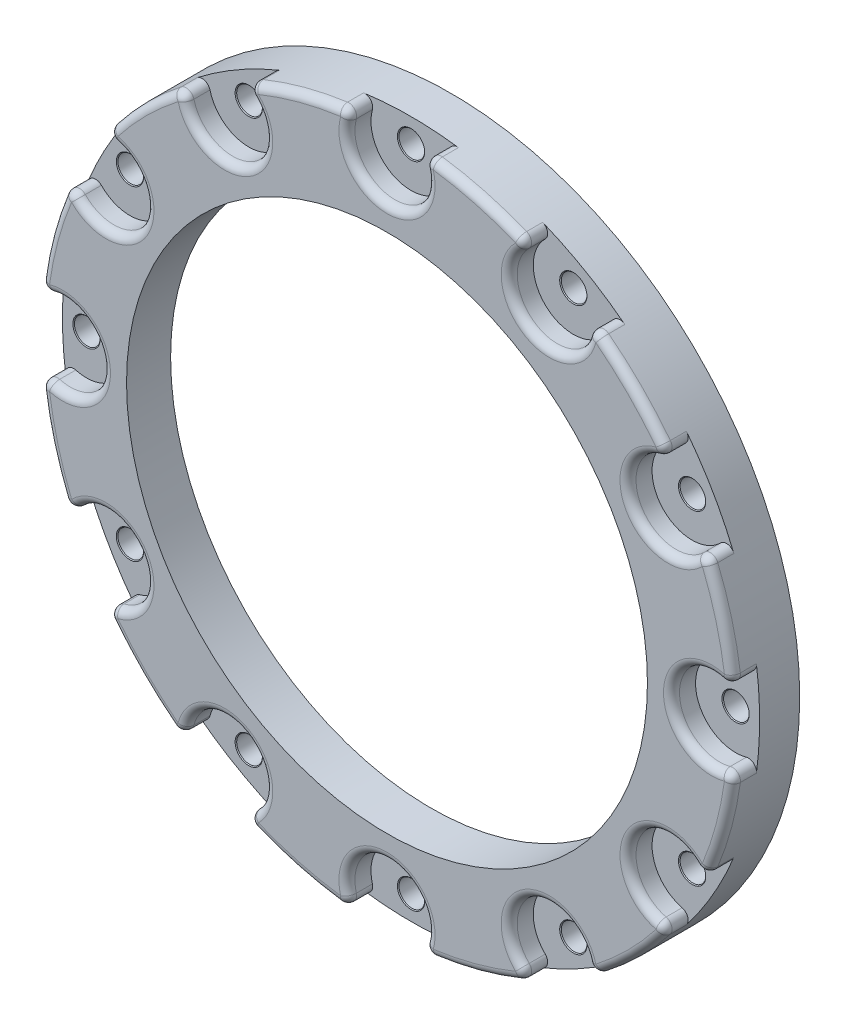
SolidWorks part; units mm, degrees
material "ABS"
ref_plane "Front Plane" through (0, 0, 0) normal (0, 0, 1) x (1, 0, 0)
ref_plane "Top Plane" through (0, 0, 0) normal (0, 1, 0) x (1, 0, 0)
ref_plane "Right Plane" through (0, 0, 0) normal (1, 0, 0) x (0, 0, -1)
sketch "Sketch1" plane through (0, 0, 0) normal (0, 0, 1) x (1, 0, 0)
  circle A0 centre (0, 0) radius 43.5
  circle A1 centre (0, 0) radius 37.5 construction
  circle A9 centre (0, 0) radius 32.5
  point P22 (0, 0)
  dimension "D1" = 87
  dimension "D2" = 75
  dimension "D5" = 65
extrude "Boss-Extrude1" add sketch "Sketch1" along normal blind 8
sketch "Sketch2" plane through (0, 0, 0) normal (0, 0, -1) x (-1, 0, 0)
  circle A0 centre (0, 0) radius 37.7
  dimension "D1" = 75.4
extrude "Cut-Extrude1" cut sketch "Sketch2" against normal blind 2.5
sketch "Sketch3" plane through (0, 0, 2.5) normal (0, 0, -1) x (-1, 0, 0)
  circle A0 centre (0, 0) radius 36.15
  circle A1 centre (0, 0) radius 33.85
  circle A2 centre (0, 0) radius 32.5 construction
  dimension "D1" = 1.35
  dimension "D2" = 2.3
extrude "Cut-Extrude2" [suppressed] cut sketch "Sketch3" against normal blind 1
sketch "Sketch4" plane through (0, 0, 8) normal (0, 0, 1) x (1, 0, 0)
  line L0 (0, 0) -> (-56.8806, 0) construction
  line L1 (-37.5, 12.7923) -> (-37.5, -12.7923) construction
  circle A0 centre (-40.5, 0) radius 1.6
  circle A1 centre (0, 0) radius 37.7 construction
  circle A2 centre (0, 0) radius 37.7 construction
  circle A3 centre (0, 0) radius 43.5 construction
  circle A4 centre (0, 0) radius 43.5 construction
  circle A5 centre (-35.074, 20.25) radius 1.6
  circle A6 centre (-20.25, 35.074) radius 1.6
  circle A7 centre (0, 40.5) radius 1.6
  circle A8 centre (20.25, 35.074) radius 1.6
  circle A9 centre (35.074, 20.25) radius 1.6
  circle A10 centre (40.5, 0) radius 1.6
  circle A11 centre (35.074, -20.25) radius 1.6
  circle A12 centre (20.25, -35.074) radius 1.6
  circle A13 centre (0, -40.5) radius 1.6
  circle A14 centre (-20.25, -35.074) radius 1.6
  circle A15 centre (-35.074, -20.25) radius 1.6
  point P10 (-37.5, 0)
  point P36 (0, 0)
  dimension "D1" = 3.2
  dimension "D2" = 3
  dimension "D3" = 75.4
  dimension "D4" = 12
extrude "Cut-Extrude3" cut sketch "Sketch4" against normal through all
ref_axis "Axis1" through (0, 0, 8) along (0, 0, -1)
sketch "Sketch5" plane through (0, 0, 8) normal (0, 0, 1) x (1, 0, 0)
  arc A0 (-4.8178, 41.8374) -> (4.8178, 41.8374) centre (0, 40.5) ccw
  arc A1 (-5.9174, 43.0956) -> (-4.8178, 41.8374) centre (-5.7814, 42.1049) cw
  arc A2 (-5.9174, 43.0956) -> (5.9174, 43.0956) centre (0, 0) ccw
  arc A3 (5.9174, 43.0956) -> (4.8178, 41.8374) centre (5.7814, 42.1049) ccw
  arc A4 (16.4232, 40.2806) -> (16.7464, 38.6412) centre (16.0457, 39.3546) cw
  arc A5 (16.7464, 38.6412) -> (25.0911, 33.8234) centre (20.25, 35.074) ccw
  arc A6 (26.6724, 34.3632) -> (25.0911, 33.8234) centre (26.0593, 33.5733) ccw
  arc A7 (34.3632, 26.6724) -> (33.8234, 25.0911) centre (33.5733, 26.0593) cw
  arc A8 (33.8234, 25.0911) -> (38.6412, 16.7464) centre (35.074, 20.25) ccw
  arc A9 (40.2806, 16.4232) -> (38.6412, 16.7464) centre (39.3546, 16.0457) ccw
  arc A10 (43.0956, 5.9174) -> (41.8374, 4.8178) centre (42.1049, 5.7814) cw
  arc A11 (41.8374, 4.8178) -> (41.8374, -4.8178) centre (40.5, 0) ccw
  arc A12 (43.0956, -5.9174) -> (41.8374, -4.8178) centre (42.1049, -5.7814) ccw
  arc A13 (40.2806, -16.4232) -> (38.6412, -16.7464) centre (39.3546, -16.0457) cw
  arc A14 (38.6412, -16.7464) -> (33.8234, -25.0911) centre (35.074, -20.25) ccw
  arc A15 (34.3632, -26.6724) -> (33.8234, -25.0911) centre (33.5733, -26.0593) ccw
  arc A16 (26.6724, -34.3632) -> (25.0911, -33.8234) centre (26.0593, -33.5733) cw
  arc A17 (25.0911, -33.8234) -> (16.7464, -38.6412) centre (20.25, -35.074) ccw
  arc A18 (16.4232, -40.2806) -> (16.7464, -38.6412) centre (16.0457, -39.3546) ccw
  arc A19 (5.9174, -43.0956) -> (4.8178, -41.8374) centre (5.7814, -42.1049) cw
  arc A20 (4.8178, -41.8374) -> (-4.8178, -41.8374) centre (0, -40.5) ccw
  arc A21 (-5.9174, -43.0956) -> (-4.8178, -41.8374) centre (-5.7814, -42.1049) ccw
  arc A22 (-16.4232, -40.2806) -> (-16.7464, -38.6412) centre (-16.0457, -39.3546) cw
  arc A23 (-16.7464, -38.6412) -> (-25.0911, -33.8234) centre (-20.25, -35.074) ccw
  arc A24 (-26.6724, -34.3632) -> (-25.0911, -33.8234) centre (-26.0593, -33.5733) ccw
  arc A25 (-34.3632, -26.6724) -> (-33.8234, -25.0911) centre (-33.5733, -26.0593) cw
  arc A26 (-33.8234, -25.0911) -> (-38.6412, -16.7464) centre (-35.074, -20.25) ccw
  arc A27 (-40.2806, -16.4232) -> (-38.6412, -16.7464) centre (-39.3546, -16.0457) ccw
  arc A28 (-43.0956, -5.9174) -> (-41.8374, -4.8178) centre (-42.1049, -5.7814) cw
  arc A29 (-41.8374, -4.8178) -> (-41.8374, 4.8178) centre (-40.5, 0) ccw
  arc A30 (-43.0956, 5.9174) -> (-41.8374, 4.8178) centre (-42.1049, 5.7814) ccw
  arc A31 (-40.2806, 16.4232) -> (-38.6412, 16.7464) centre (-39.3546, 16.0457) cw
  arc A32 (-38.6412, 16.7464) -> (-33.8234, 25.0911) centre (-35.074, 20.25) ccw
  arc A33 (-34.3632, 26.6724) -> (-33.8234, 25.0911) centre (-33.5733, 26.0593) ccw
  arc A34 (-26.6724, 34.3632) -> (-25.0911, 33.8234) centre (-26.0593, 33.5733) cw
  arc A35 (-25.0911, 33.8234) -> (-16.7464, 38.6412) centre (-20.25, 35.074) ccw
  arc A36 (-16.4232, 40.2806) -> (-16.7464, 38.6412) centre (-16.0457, 39.3546) ccw
  point P89 (0, 0)
  circle M1 centre (-35.074, 20.25) radius 1.6
  circle M2 centre (-20.25, 35.074) radius 1.6
  circle M3 centre (0, 40.5) radius 1.6
  circle M4 centre (20.25, 35.074) radius 1.6
  circle M5 centre (35.074, 20.25) radius 1.6
  circle M6 centre (40.5, 0) radius 1.6
  circle M7 centre (35.074, -20.25) radius 1.6
  circle M8 centre (20.25, -35.074) radius 1.6
  circle M9 centre (0, -40.5) radius 1.6
  circle M10 centre (-20.25, -35.074) radius 1.6
  circle M11 centre (-35.074, -20.25) radius 1.6
  circle M12 centre (-40.5, 0) radius 1.6
  circle M13 centre (0, 0) radius 43.5
  dimension "D1" = 10
  dimension "D2" = 1
  dimension "D3" = 1
  dimension "D4" = 12
extrude "Cut-Extrude4" cut sketch "Sketch5" against normal blind 3 contours A3 A1 A0 M13 M3 | A6 A2 A4 A5 M4 | A9 A2 A7 A8 M5 | A12 A2 A10 A11 M6 | A15 A2 A13 A14 M7 | A18 A2 A16 A17 M8 | A21 A2 A19 A20 M9 | A24 A2 A22 A23 M10 | A27 A2 A25 A26 M11 | A30 A2 A28 A29 M12 | A33 A2 A31 A32 M1 | A36 A2 A34 A35 M2 region at (-4.9208, 42.857, 8) region at (-17.1771, 39.5777, 8) region at (21.6734, 37.5394, 8) region at (-34.6646, 25.6867, 8) region at (37.5394, 21.6734, 8) region at (-42.857, 4.9208, 8) region at (43.2563, 2.9559, 8) region at (-39.5777, -17.1771, 8) region at (37.5394, -21.6734, 8) region at (-25.6867, -34.6646, 8) region at (21.6734, -37.5394, 8) region at (-4.9208, -42.857, 8)
fillet "Fillet1" radius 1 48 edges at (17.0268, 39.548, 8) (11.2586, 42.0178, 8) (5.0284, 42.763, 8) (0, 35.5, 8) (-5.0284, 42.763, 8) (-11.2586, 42.0178, 8) (-17.0268, 39.548, 8) (-17.75, 30.7439, 8) (-25.7362, 34.5196, 8) (-30.7591, 30.7591, 8) (-34.5196, 25.7362, 8) (-30.7439, 17.75, 8) (-39.548, 17.0268, 8) (-42.0178, 11.2586, 8) (-42.763, 5.0284, 8) (-35.5, 0, 8) (-42.763, -5.0284, 8) (-42.0178, -11.2586, 8) (-39.548, -17.0268, 8) (-30.7439, -17.75, 8) (-34.5196, -25.7362, 8) (-30.7591, -30.7591, 8) (-25.7362, -34.5196, 8) (-17.75, -30.7439, 8) (-17.0268, -39.548, 8) (-11.2586, -42.0178, 8) (-5.0284, -42.763, 8) (0, -35.5, 8) (5.0284, -42.763, 8) (11.2586, -42.0178, 8) (17.0268, -39.548, 8) (17.75, -30.7439, 8) (25.7362, -34.5196, 8) (30.7591, -30.7591, 8) (34.5196, -25.7362, 8) (30.7439, -17.75, 8) (39.548, -17.0268, 8) (42.0178, -11.2586, 8) (42.763, -5.0284, 8) (35.5, 0, 8) (42.763, 5.0284, 8) (42.0178, 11.2586, 8) (39.548, 17.0268, 8) (30.7439, 17.75, 8) (34.5196, 25.7362, 8) (30.7591, 30.7591, 8) (25.7362, 34.5196, 8) (17.75, 30.7439, 8)
chamfer "Chamfer1" distance 0.1 angle 45 12 edges at (-33.474, 20.25, 5) (-18.65, 35.074, 5) (1.6, 40.5, 5) (21.85, 35.074, 5) (36.674, 20.25, 5) (42.1, 0, 5) (36.674, -20.25, 5) (21.85, -35.074, 5) (1.6, -40.5, 5) (-18.65, -35.074, 5) (-33.474, -20.25, 5) (-38.9, 0, 5)
fillet "Fillet2" radius 0.5 1 edges at (-37.7, 0, 2.5)
